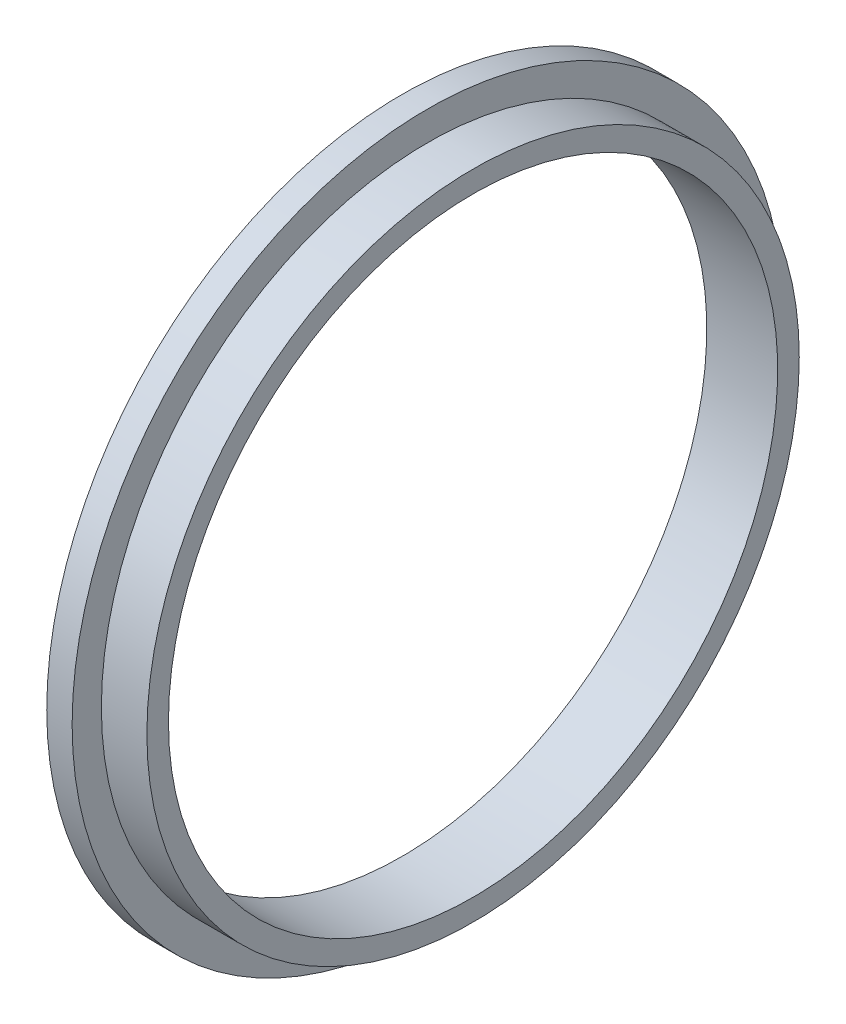
SolidWorks part; units mm, degrees
material "Nylon 101"
ref_plane "Front Plane" through (0, 0, 0) normal (0, 0, 1) x (1, 0, 0)
ref_plane "Top Plane" through (0, 0, 0) normal (0, 1, 0) x (1, 0, 0)
ref_plane "Right Plane" through (0, 0, 0) normal (1, 0, 0) x (0, 0, -1)
sketch "Sketch1" plane through (0, 0, 0) normal (1, 0, 0) x (0, 0, -1)
  circle A0 centre (0, 0) radius 10.2
  circle A1 centre (0, 0) radius 11.9011
  dimension "D1" = 20.4
  dimension "D2" = 23.8022
extrude "Boss-Extrude1" add sketch "Sketch1" along normal blind 0.85
sketch "Sketch2" plane through (0.85, 0, 0) normal (1, 0, 0) x (0, 0, -1)
  circle A0 centre (0, 0) radius 10.922
  circle A1 centre (0, 0) radius 10.2 construction
  circle A2 centre (0, 0) radius 10.2
  dimension "D1" = 21.844
extrude "Boss-Extrude2" add sketch "Sketch2" along normal blind 1.524
equation "\"D2@Sketch1\"=11.9011mm*2"
equation "\"D1@Boss-Extrude1\"=0.85mm"
